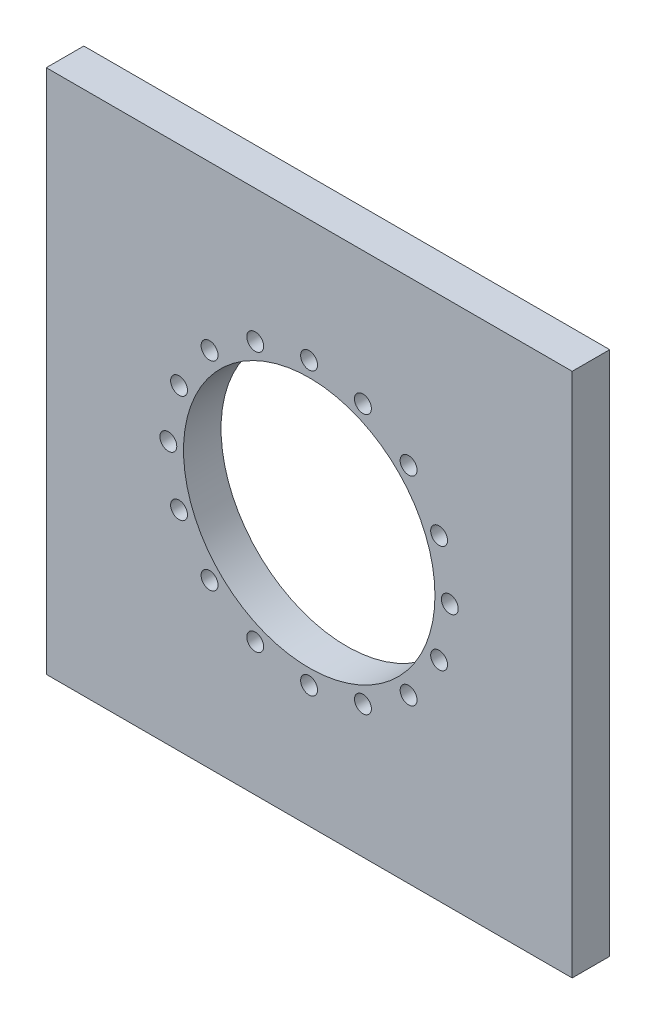
SolidWorks part; units mm, degrees
material "6061 Alloy"
ref_plane "Front Plane" through (0, 0, 0) normal (0, 0, 1) x (1, 0, 0)
ref_plane "Top Plane" through (0, 0, 0) normal (0, 1, 0) x (1, 0, 0)
ref_plane "Right Plane" through (0, 0, 0) normal (1, 0, 0) x (0, 0, -1)
sketch "Sketch2" plane through (0, 0, 0) normal (0, 0, 1) x (1, 0, 0)
  circle A2 centre (-107.5487, 34.6455) radius 2.25
  circle A3 centre (-95.3828, 26.5165) radius 2.25
  circle A4 centre (-87.2538, 14.3506) radius 2.25
  circle A5 centre (-84.3993, 0) radius 2.25
  circle A6 centre (-87.2538, -14.3506) radius 2.25
  circle A7 centre (-95.3828, -26.5165) radius 2.25
  circle A8 centre (-107.5487, -34.6455) radius 2.25
  circle A9 centre (-121.8993, -37.5) radius 2.25
  circle A10 centre (-136.2499, -34.6455) radius 2.25
  circle A11 centre (-148.4158, -26.5165) radius 2.25
  circle A12 centre (-156.5448, -14.3506) radius 2.25
  circle A13 centre (-159.3993, 0) radius 2.25
  circle A14 centre (-156.5448, 14.3506) radius 2.25
  circle A15 centre (-148.4158, 26.5165) radius 2.25
  circle A16 centre (-136.2499, 34.6455) radius 2.25
  circle A17 centre (-121.8993, 37.5) radius 2.25
sketch "Sketch3" plane through (0, 0, 0) normal (0, 0, 1) x (1, 0, 0)
  line L1 (-191.9216, -70) -> (-51.7906, -70)
  line L2 (-191.9216, -70) -> (-191.9216, 70)
  line L3 (-191.9216, 70) -> (-51.7906, 70)
  line L4 (-51.7906, -70) -> (-51.7906, 70)
  line L5 (-191.9216, -70) -> (-51.7906, 70) construction
  line L6 (-191.9216, 70) -> (-51.7906, -70) construction
  circle A22 centre (-121.8561, 0) radius 33.5
  point P5 (0, 0)
  point P6 (-118.6649, 1.8898)
  point P7 (-119.3787, 2.1205)
  point P8 (-120.4507, 0)
  point P9 (-119.9147, 0)
  point P10 (-121.7906, 0)
extrude "Boss-Extrude3" add sketch "Sketch3" along normal blind 10 contours L3 L4 L1 L2
extrude "Cut-Extrude5" cut sketch "Sketch3<7>" along normal blind 10 flip side to cut
sketch "Sketch3<7>" plane through (0, 0, 0) normal (0, 0, 1) x (1, 0, 0) same geometry as "Sketch3"
extrude "Cut-Extrude6" cut sketch "Sketch2" along normal blind 10
